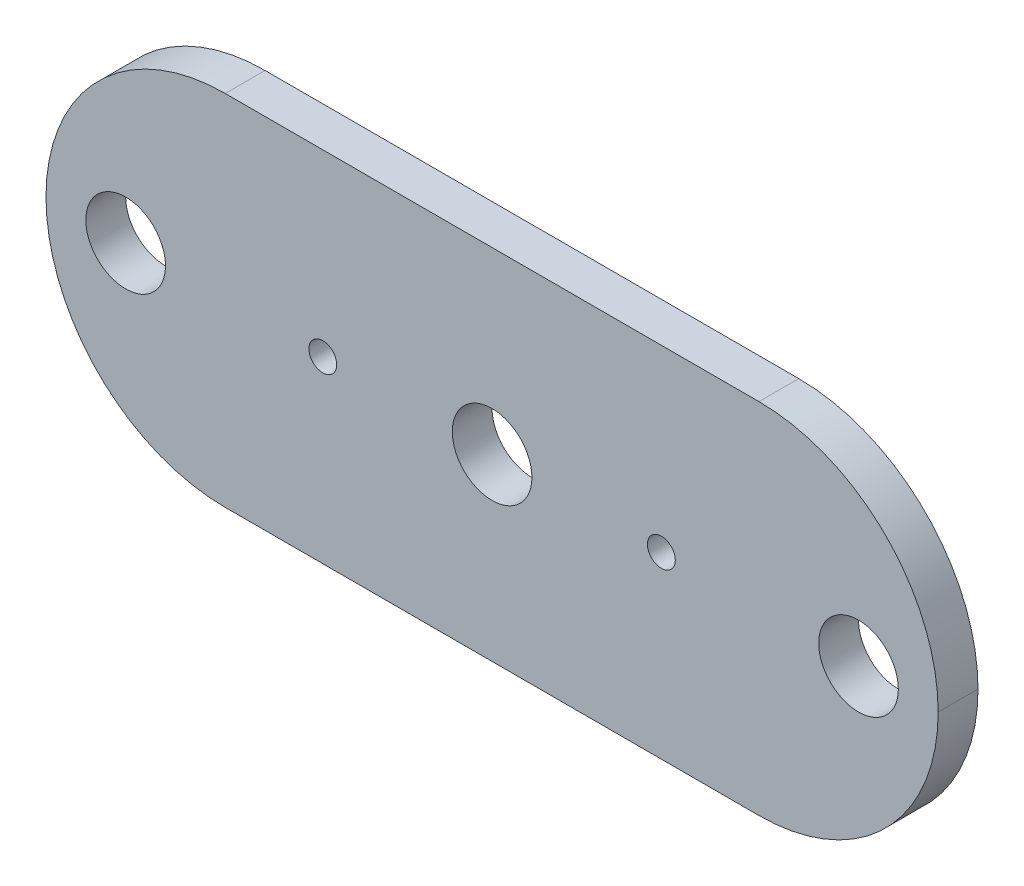
SolidWorks part; units mm, degrees
ref_plane "Plan de face" through (0, 0, 0) normal (0, 0, 1) x (1, 0, 0)
ref_plane "Plan de dessus" through (0, 0, 0) normal (0, 1, 0) x (1, 0, 0)
ref_plane "Plan de droite" through (0, 0, 0) normal (1, 0, 0) x (0, 0, -1)
sketch "Esquisse1" plane through (0, 0, 0) normal (0, 0, 1) x (1, 0, 0)
  line L4 (-56, 22.5) -> (56, 22.5)
  line L5 (-56, 22.5) -> (-56, -22.5)
  line L6 (-56, -22.5) -> (56, -22.5)
  line L7 (56, -22.5) -> (56, 22.5)
  line L8 (-56, 0) -> (56, 0) construction
  line L9 (0, 22.5) -> (0, -22.5) construction
  arc A0 (-28.1025, 22.5) -> (-28.1025, -22.5) centre (0, 0) ccw construction
  arc A1 (28.1025, 22.5) -> (-28.1025, 22.5) centre (0, 0) ccw construction
  arc A2 (28.1025, -22.5) -> (28.1025, 22.5) centre (0, 0) ccw construction
  arc A3 (-28.1025, -22.5) -> (28.1025, -22.5) centre (0, 0) ccw construction
  circle A4 centre (21.25, 0) radius 1.75
  circle A5 centre (-21.25, 0) radius 1.75
  circle A6 centre (46, 0) radius 5
  circle A7 centre (-46, 0) radius 5
  circle A8 centre (0, 0) radius 5
  dimension "D1" = 72
  dimension "D6" = 3.5
  dimension "D7" = 21.25
  dimension "D8" = 10
  dimension "D9" = 10
  dimension "D10" = 10
  dimension "D2" = 22.5
  dimension "D3" = 45
  dimension "D4" = 56
  dimension "D5" = 56
extrude "Boss.-Extru.1" add sketch "Esquisse1" along normal blind 5
fillet "Congé1" radius 22.5 4 edges at (-56, -22.5, 2.5) (-56, 22.5, 2.5) (56, -22.5, 2.5) (56, 22.5, 2.5)
